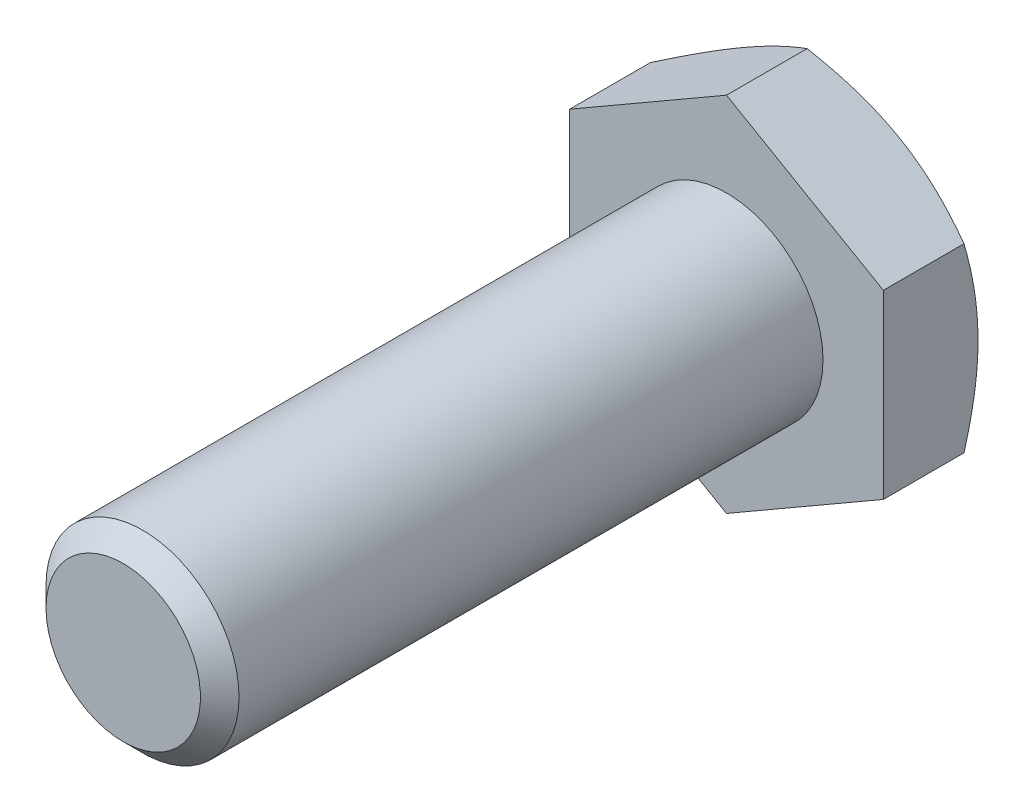
SolidWorks part; units mm, degrees
ref_plane "Plan1" through (0, 0, 0) normal (0, 0, 1) x (1, 0, 0)
ref_plane "Plan2" through (0, 0, 0) normal (0, 1, 0) x (1, 0, 0)
ref_plane "Plan3" through (0, 0, 0) normal (1, 0, 0) x (0, 0, -1)
sketch "Esquisse1" plane through (0, 0, 0) normal (0, 1, 0) x (1, 0, 0)
  line L1 (0, 0) -> (0, -25) construction
  line L2 (0, 0) -> (4, 0)
  line L3 (0, 0) -> (0, -25)
  line L4 (0, -25) -> (4, -25)
  line L6 (4, 0) -> (4, -25)
  dimension "D1" = 25
  dimension "D2" = 4
revolve "Base-Révolution" add sketch "Esquisse1" angle 360 about L1 reverse direction yes
chamfer "Chanfrein1" distance 0.8 angle 45 1 edges at (4, 0, 25)
sketch "Esquisse3" plane through (0, 0, 0) normal (0, 1, 0) x (1, 0, 0)
  line L0 (4, -24.2) -> (4, 0) construction
  line L1 (-3.2, -25) -> (3.2, -25) construction
  line L2 (3.25, -25) -> (3.25, -24.925)
  line L3 (3.25, -24.925) -> (4.075, -24.4487)
  line L4 (3.25, -25) -> (3.25, -25.075)
  line L5 (3.25, -25.075) -> (4.075, -25.5513)
  line L6 (4.075, -24.4487) -> (4.075, -25.5513)
  point P0 (10, -20)
  point P1 (4, -25)
  dimension "D1" = 0.75
  dimension "D2" = 0.075
  dimension "D3" = 0.825
  dimension "D4" = 0.075
  dimension "D5" = 60
  dimension "D6" = 60
sketch "Esquisse4" plane through (0, 0, 25) normal (0, 0, 1) x (1, 0, 0)
  circle A0 centre (0, 0) radius 4 construction
  circle A1 centre (0, 0) radius 4
curve "Hélice1" pitch 1.25 height 22 turns 17.6
sweep "Enlèvement de matière-Balayage3" [suppressed] cut profiles "Esquisse3" path "Hélice1"
sketch "Esquisse6" plane through (0, 0, 0) normal (0, 0, 1) x (1, 0, 0)
  line L0 (0, 0) -> (6.5, 0) construction
  line L1 (6.5, -3.7528) -> (6.5, 3.7528)
  line L2 (0, 0) -> (6.5, 3.7528) construction
  line L3 (0, 7.5056) -> (6.5, 3.7528)
  line L4 (0, -7.5056) -> (6.5, -3.7528)
  line L5 (0, 0) -> (0, 6.5) construction
  line L6 (-6.5, -3.7528) -> (-6.5, 3.7528)
  line L7 (-6.5, 3.7528) -> (0, 7.5056)
  line L8 (0, -7.5056) -> (-6.5, -3.7528)
  circle A0 centre (0, 0) radius 6.5 construction
  dimension "D2" = 30
  dimension "D1" = 13
extrude "Boss.-Extru.1" add sketch "Esquisse6" against normal blind 4.5
sketch "Esquisse7" plane through (0, 0, 0) normal (0, 1, 0) x (1, 0, 0)
  line L0 (-5.5, 4.5) -> (-13.2942, 4.5)
  line L1 (-5.5, 4.5) -> (-13.2942, 0)
  line L2 (-13.2942, 4.5) -> (-13.2942, 0)
  line L3 (0, 6.2394) -> (0, 0) construction
  line L4 (0, -24.2) -> (0, -25) construction
  line L5 (-6.5, 4.5) -> (0, 4.5) construction
  dimension "D1" = 30
  dimension "D2" = 5.5
revolve "Enlèvement de matière-Révolution1" cut sketch "Esquisse7" angle 360 about L3
equation "\"D1@Chanfrein1\"=\"D2@Esquisse1\"*0.2"
equation "\"D2@Esquisse3\"=0.1*\"D1@Esquisse3\""
equation "\"D4@Esquisse3\" = 0.1*\"D1@Esquisse3\""
equation "\"D3@Esquisse3\"=1.1*\"D1@Esquisse3\""
equation "\"D1@Esquisse3\"=0.6*\"D4@Hélice1\""
